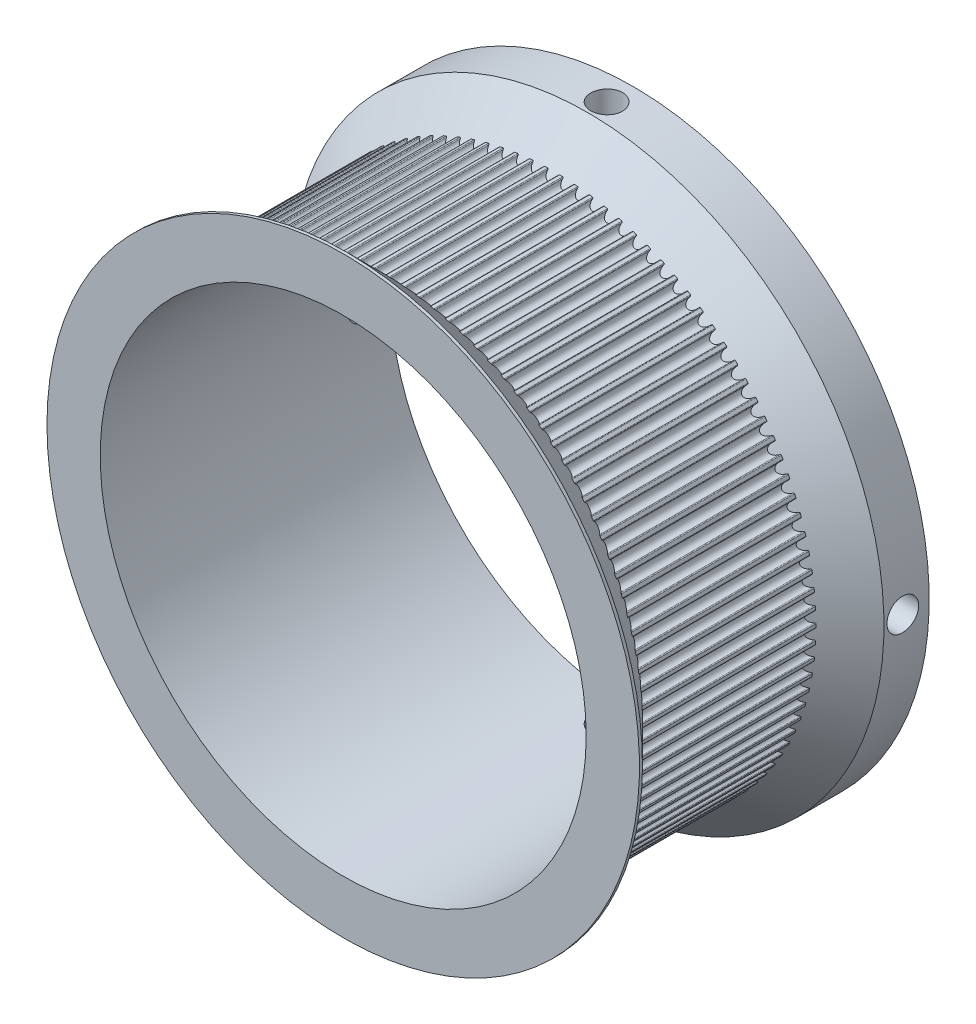
SolidWorks part; units mm, degrees
ref_plane "Front Plane" through (0, 0, 0) normal (0, 0, 1) x (1, 0, 0)
ref_plane "Top Plane" through (0, 0, 0) normal (0, 1, 0) x (1, 0, 0)
ref_plane "Right Plane" through (0, 0, 0) normal (1, 0, 0) x (0, 0, -1)
sketch "Sketch2" plane through (0, 0, 0) normal (0, 0, 1) x (1, 0, 0)
  circle A0 centre (0, 0) radius 35.0141 construction
  arc A1 (-2.7736, 34.6493) -> (-2.6556, 34.5527) centre (-2.7648, 34.5396) cw
  arc A2 (-2.6556, 34.5527) -> (-1.3004, 34.6302) centre (-1.9804, 34.6335) ccw
  arc A3 (-1.3004, 34.6302) -> (-1.1942, 34.7396) centre (-1.1904, 34.6296) cw
  arc A4 (-1.1942, 34.7396) -> (-0.791, 34.7511) centre (0, 0) cw
  circle A5 centre (0, 0) radius 34.7601 construction
  circle A6 centre (0, 0) radius 34.0101 construction
  arc A7 (0.791, 34.7511) -> (1.1942, 34.7396) centre (0, 0) cw
  arc A8 (0.6787, 34.6479) -> (0.791, 34.7511) centre (0.7885, 34.6411) cw
  arc A9 (-0.6787, 34.6479) -> (0.6787, 34.6479) centre (0, 34.6901) ccw
  arc A10 (-0.791, 34.7511) -> (-0.6787, 34.6479) centre (-0.7885, 34.6411) cw
  arc A11 (2.7736, 34.6493) -> (3.1755, 34.6147) centre (0, 0) cw
  arc A12 (2.6556, 34.5527) -> (2.7736, 34.6493) centre (2.7648, 34.5396) cw
  arc A13 (1.3004, 34.6302) -> (2.6556, 34.5527) centre (1.9804, 34.6335) ccw
  arc A14 (1.1942, 34.7396) -> (1.3004, 34.6302) centre (1.1904, 34.6296) cw
  arc A15 (4.7472, 34.4344) -> (5.1464, 34.377) centre (0, 0) cw
  arc A16 (4.6238, 34.3447) -> (4.7472, 34.4344) centre (4.7321, 34.3254) cw
  arc A17 (3.2753, 34.4995) -> (4.6238, 34.3447) centre (3.9544, 34.464) ccw
  arc A18 (3.1755, 34.6147) -> (3.2753, 34.4995) centre (3.1654, 34.5052) cw
  arc A19 (6.7052, 34.1072) -> (7.1006, 34.0271) centre (0, 0) cw
  arc A20 (6.577, 34.0247) -> (6.7052, 34.1072) centre (6.684, 33.9993) cw
  arc A21 (5.2395, 34.2562) -> (6.577, 34.0247) centre (5.9154, 34.182) ccw
  arc A22 (5.1464, 34.377) -> (5.2395, 34.2562) centre (5.1301, 34.2682) cw
  arc A23 (8.6414, 33.6688) -> (9.0316, 33.5663) centre (0, 0) cw
  arc A24 (8.5087, 33.5938) -> (8.6414, 33.6688) centre (8.6141, 33.5623) cw
  arc A25 (7.1866, 33.9012) -> (8.5087, 33.5938) centre (7.8572, 33.7886) ccw
  arc A26 (7.1006, 34.0271) -> (7.1866, 33.9012) centre (7.0781, 33.9194) cw
  arc A27 (10.5495, 33.1206) -> (10.9331, 32.9959) centre (0, 0) cw
  arc A28 (10.4127, 33.0532) -> (10.5495, 33.1206) centre (10.5161, 33.0158) cw
  arc A29 (9.1103, 33.4357) -> (10.4127, 33.0532) centre (9.7733, 33.2849) ccw
  arc A30 (9.0316, 33.5663) -> (9.1103, 33.4357) centre (9.003, 33.46) cw
  arc A31 (12.4231, 32.4643) -> (12.799, 32.318) centre (0, 0) cw
  arc A32 (12.2826, 32.4049) -> (12.4231, 32.4643) centre (12.3838, 32.3616) cw
  arc A33 (11.0042, 32.861) -> (12.2826, 32.4049) centre (11.6576, 32.6727) ccw
  arc A34 (10.9331, 32.9959) -> (11.0042, 32.861) centre (10.8985, 32.8915) cw
  arc A35 (14.2562, 31.7021) -> (14.6231, 31.5346) centre (0, 0) cw
  arc A36 (14.1126, 31.6508) -> (14.2562, 31.7021) centre (14.211, 31.6018) cw
  arc A37 (12.8622, 32.1792) -> (14.1126, 31.6508) centre (13.5038, 31.9539) ccw
  arc A38 (12.799, 32.318) -> (12.8622, 32.1792) centre (12.7585, 32.2157) cw
  arc A39 (16.0427, 30.8366) -> (16.3995, 30.6483) centre (0, 0) cw
  arc A40 (15.8965, 30.7935) -> (16.0427, 30.8366) centre (15.992, 30.739) cw
  arc A41 (14.6783, 31.3925) -> (15.8965, 30.7935) centre (15.306, 31.1308) ccw
  arc A42 (14.6231, 31.5346) -> (14.6783, 31.3925) centre (14.5768, 31.4348) cw
  arc A43 (17.777, 29.8704) -> (18.1224, 29.6621) centre (0, 0) cw
  arc A44 (17.6285, 29.8358) -> (17.777, 29.8704) centre (17.7207, 29.7759) cw
  arc A45 (16.4466, 30.5033) -> (17.6285, 29.8358) centre (17.0583, 30.2063) ccw
  arc A46 (16.3995, 30.6483) -> (16.4466, 30.5033) centre (16.3476, 30.5513) cw
  arc A47 (19.4533, 28.8068) -> (19.7863, 28.5791) centre (0, 0) cw
  arc A48 (19.303, 28.7808) -> (19.4533, 28.8068) centre (19.3917, 28.7157) cw
  arc A49 (18.1611, 29.5146) -> (19.303, 28.7808) centre (18.7549, 29.1832) ccw
  arc A50 (18.1224, 29.6621) -> (18.1611, 29.5146) centre (18.0651, 29.5682) cw
  arc A51 (21.0661, 27.6493) -> (21.3855, 27.403) centre (0, 0) cw
  arc A52 (20.9146, 27.6318) -> (21.0661, 27.6493) centre (20.9994, 27.5618) cw
  arc A53 (19.8165, 28.4297) -> (20.9146, 27.6318) centre (20.3903, 28.0649) ccw
  arc A54 (19.7863, 28.5791) -> (19.8165, 28.4297) centre (19.7236, 28.4887) cw
  arc A55 (22.6102, 26.4016) -> (22.9151, 26.1374) centre (0, 0) cw
  arc A56 (22.458, 26.3928) -> (22.6102, 26.4016) centre (22.5387, 26.318) cw
  arc A57 (21.4072, 27.252) -> (22.458, 26.3928) centre (21.9593, 26.855) ccw
  arc A58 (21.3855, 27.403) -> (21.4072, 27.252) centre (21.3179, 27.3162) cw
  arc A59 (24.0806, 25.0677) -> (24.3698, 24.7866) centre (0, 0) cw
  arc A60 (23.9281, 25.0676) -> (24.0806, 25.0677) centre (24.0044, 24.9884) cw
  arc A61 (22.928, 25.9855) -> (23.9281, 25.0676) centre (23.4566, 25.5576) ccw
  arc A62 (22.9151, 26.1374) -> (22.928, 25.9855) centre (22.8425, 26.0547) cw
  arc A63 (25.4724, 23.6521) -> (25.7451, 23.3549) centre (0, 0) cw
  arc A64 (25.3201, 23.6607) -> (25.4724, 23.6521) centre (25.3918, 23.5773) cw
  arc A65 (24.3741, 24.6342) -> (25.3201, 23.6607) centre (24.8774, 24.1768) ccw
  arc A66 (24.3698, 24.7866) -> (24.3741, 24.6342) centre (24.2927, 24.7081) cw
  arc A67 (26.7811, 22.1593) -> (27.0365, 21.8471) centre (0, 0) cw
  arc A68 (26.6296, 22.1767) -> (26.7811, 22.1593) centre (26.6964, 22.0892) cw
  arc A69 (25.7407, 23.2025) -> (26.6296, 22.1767) centre (26.217, 22.7172) ccw
  arc A70 (25.7451, 23.3549) -> (25.7407, 23.2025) centre (25.6637, 23.281) cw
  arc A71 (28.0025, 20.5943) -> (28.2396, 20.268) centre (0, 0) cw
  arc A72 (27.8522, 20.6202) -> (28.0025, 20.5943) centre (27.9139, 20.5291) cw
  arc A73 (27.0233, 21.6951) -> (27.8522, 20.6202) centre (27.4712, 21.1834) ccw
  arc A74 (27.0365, 21.8471) -> (27.0233, 21.6951) centre (26.9509, 21.7779) cw
  arc A75 (29.1325, 18.9621) -> (29.3506, 18.6227) centre (0, 0) cw
  arc A76 (28.984, 18.9966) -> (29.1325, 18.9621) centre (29.0403, 18.9021) cw
  arc A77 (28.2178, 20.117) -> (28.984, 18.9966) centre (28.6357, 19.5806) ccw
  arc A78 (28.2396, 20.268) -> (28.2178, 20.117) centre (28.1502, 20.2038) cw
  arc A79 (30.1675, 17.268) -> (30.3659, 16.9168) centre (0, 0) cw
  arc A80 (30.0212, 17.3109) -> (30.1675, 17.268) centre (30.0721, 17.2134) cw
  arc A81 (29.3202, 18.4733) -> (30.0212, 17.3109) centre (29.7068, 17.9139) ccw
  arc A82 (29.3506, 18.6227) -> (29.3202, 18.4733) centre (29.2577, 18.5638) cw
  arc A83 (31.1041, 15.5176) -> (31.2821, 15.1556) centre (0, 0) cw
  arc A84 (30.9605, 15.5688) -> (31.1041, 15.5176) centre (31.0057, 15.4685) cw
  arc A85 (30.3271, 16.7693) -> (30.9605, 15.5688) centre (30.6811, 16.1887) ccw
  arc A86 (30.3659, 16.9168) -> (30.3271, 16.7693) centre (30.2698, 16.8632) cw
  arc A87 (31.9393, 13.7166) -> (32.0963, 13.3451) centre (0, 0) cw
  arc A88 (31.7988, 13.7759) -> (31.9393, 13.7166) centre (31.8382, 13.6732) cw
  arc A89 (31.2349, 15.0106) -> (31.7988, 13.7759) centre (31.5552, 14.4108) ccw
  arc A90 (31.2821, 15.1556) -> (31.2349, 15.0106) centre (31.1831, 15.1077) cw
  arc A91 (32.6703, 11.8709) -> (32.8058, 11.4909) centre (0, 0) cw
  arc A92 (32.5334, 11.9381) -> (32.6703, 11.8709) centre (32.5669, 11.8333) cw
  arc A93 (32.0409, 13.203) -> (32.5334, 11.9381) centre (32.3264, 12.5858) ccw
  arc A94 (32.0963, 13.3451) -> (32.0409, 13.203) centre (31.9947, 13.3028) cw
  arc A95 (33.2947, 9.9864) -> (33.4083, 9.5994) centre (0, 0) cw
  arc A96 (33.1619, 10.0613) -> (33.2947, 9.9864) centre (33.1893, 9.9548) cw
  arc A97 (32.7424, 11.3523) -> (33.1619, 10.0613) centre (32.9922, 10.7198) ccw
  arc A98 (32.8058, 11.4909) -> (32.7424, 11.3523) centre (32.702, 11.4546) cw
  arc A99 (33.8105, 8.0694) -> (33.9019, 7.6765) centre (0, 0) cw
  arc A100 (33.6822, 8.1517) -> (33.8105, 8.0694) centre (33.7035, 8.0438) cw
  arc A101 (33.3371, 9.4645) -> (33.6822, 8.1517) centre (33.5504, 8.8189) ccw
  arc A102 (33.4083, 9.5994) -> (33.3371, 9.4645) centre (33.3026, 9.569) cw
  arc A103 (34.216, 6.126) -> (34.2848, 5.7285) centre (0, 0) cw
  arc A104 (34.0926, 6.2156) -> (34.216, 6.126) centre (34.1077, 6.1066) cw
  arc A105 (33.8231, 7.5459) -> (34.0926, 6.2156) centre (33.9991, 6.8891) ccw
  arc A106 (33.9019, 7.6765) -> (33.8231, 7.5459) centre (33.7946, 7.6522) cw
  arc A107 (34.5099, 4.1627) -> (34.5559, 3.7619) centre (0, 0) cw
  arc A108 (34.3919, 4.2591) -> (34.5099, 4.1627) centre (34.4007, 4.1495) cw
  arc A109 (34.1987, 5.6027) -> (34.3919, 4.2591) centre (34.337, 4.9369) ccw
  arc A110 (34.2848, 5.7285) -> (34.1987, 5.6027) centre (34.1763, 5.7104) cw
  arc A111 (34.6913, 2.1857) -> (34.7143, 1.783) centre (0, 0) cw
  arc A112 (34.5789, 2.2888) -> (34.6913, 2.1857) centre (34.5815, 2.1788) cw
  arc A113 (34.4628, 3.6412) -> (34.5789, 2.2888) centre (34.5628, 2.9686) ccw
  arc A114 (34.5559, 3.7619) -> (34.4628, 3.6412) centre (34.4466, 3.75) cw
  arc A115 (34.7595, 0.2017) -> (34.7595, -0.2017) centre (0, 0) cw
  arc A116 (34.6532, 0.311) -> (34.7595, 0.2017) centre (34.6495, 0.2011) cw
  arc A117 (34.6144, 1.6678) -> (34.6532, 0.311) centre (34.6759, 0.9906) ccw
  arc A118 (34.7143, 1.783) -> (34.6144, 1.6678) centre (34.6045, 1.7774) cw
  arc A119 (34.7143, -1.783) -> (34.6913, -2.1857) centre (0, 0) cw
  arc A120 (34.6144, -1.6678) -> (34.7143, -1.783) centre (34.6045, -1.7774) cw
  arc A121 (34.6532, -0.311) -> (34.6144, -1.6678) centre (34.6759, -0.9906) ccw
  arc A122 (34.7595, -0.2017) -> (34.6532, -0.311) centre (34.6495, -0.2011) cw
  arc A123 (34.5559, -3.7619) -> (34.5099, -4.1627) centre (0, 0) cw
  arc A124 (34.4628, -3.6412) -> (34.5559, -3.7619) centre (34.4466, -3.75) cw
  arc A125 (34.5789, -2.2888) -> (34.4628, -3.6412) centre (34.5628, -2.9686) ccw
  arc A126 (34.6913, -2.1857) -> (34.5789, -2.2888) centre (34.5815, -2.1788) cw
  arc A127 (34.2848, -5.7285) -> (34.216, -6.126) centre (0, 0) cw
  arc A128 (34.1987, -5.6027) -> (34.2848, -5.7285) centre (34.1763, -5.7104) cw
  arc A129 (34.3919, -4.2591) -> (34.1987, -5.6027) centre (34.337, -4.9369) ccw
  arc A130 (34.5099, -4.1627) -> (34.3919, -4.2591) centre (34.4007, -4.1495) cw
  arc A131 (33.9019, -7.6765) -> (33.8105, -8.0694) centre (0, 0) cw
  arc A132 (33.8231, -7.5459) -> (33.9019, -7.6765) centre (33.7946, -7.6522) cw
  arc A133 (34.0926, -6.2156) -> (33.8231, -7.5459) centre (33.9991, -6.8891) ccw
  arc A134 (34.216, -6.126) -> (34.0926, -6.2156) centre (34.1077, -6.1066) cw
  arc A135 (33.4083, -9.5994) -> (33.2947, -9.9864) centre (0, 0) cw
  arc A136 (33.3371, -9.4645) -> (33.4083, -9.5994) centre (33.3026, -9.569) cw
  arc A137 (33.6822, -8.1517) -> (33.3371, -9.4645) centre (33.5504, -8.8189) ccw
  arc A138 (33.8105, -8.0694) -> (33.6822, -8.1517) centre (33.7035, -8.0438) cw
  arc A139 (32.8058, -11.4909) -> (32.6703, -11.8709) centre (0, 0) cw
  arc A140 (32.7424, -11.3523) -> (32.8058, -11.4909) centre (32.702, -11.4546) cw
  arc A141 (33.1619, -10.0613) -> (32.7424, -11.3523) centre (32.9922, -10.7198) ccw
  arc A142 (33.2947, -9.9864) -> (33.1619, -10.0613) centre (33.1893, -9.9548) cw
  arc A143 (32.0963, -13.3451) -> (31.9393, -13.7166) centre (0, 0) cw
  arc A144 (32.0409, -13.203) -> (32.0963, -13.3451) centre (31.9947, -13.3028) cw
  arc A145 (32.5334, -11.9381) -> (32.0409, -13.203) centre (32.3264, -12.5858) ccw
  arc A146 (32.6703, -11.8709) -> (32.5334, -11.9381) centre (32.5669, -11.8333) cw
  arc A147 (31.2821, -15.1556) -> (31.1041, -15.5176) centre (0, 0) cw
  arc A148 (31.2349, -15.0106) -> (31.2821, -15.1556) centre (31.1831, -15.1077) cw
  arc A149 (31.7988, -13.7759) -> (31.2349, -15.0106) centre (31.5552, -14.4108) ccw
  arc A150 (31.9393, -13.7166) -> (31.7988, -13.7759) centre (31.8382, -13.6732) cw
  arc A151 (30.3659, -16.9168) -> (30.1675, -17.268) centre (0, 0) cw
  arc A152 (30.3271, -16.7693) -> (30.3659, -16.9168) centre (30.2698, -16.8632) cw
  arc A153 (30.9605, -15.5688) -> (30.3271, -16.7693) centre (30.6811, -16.1887) ccw
  arc A154 (31.1041, -15.5176) -> (30.9605, -15.5688) centre (31.0057, -15.4685) cw
  arc A155 (29.3506, -18.6227) -> (29.1325, -18.9621) centre (0, 0) cw
  arc A156 (29.3202, -18.4733) -> (29.3506, -18.6227) centre (29.2577, -18.5638) cw
  arc A157 (30.0212, -17.3109) -> (29.3202, -18.4733) centre (29.7068, -17.9139) ccw
  arc A158 (30.1675, -17.268) -> (30.0212, -17.3109) centre (30.0721, -17.2134) cw
  arc A159 (28.2396, -20.268) -> (28.0025, -20.5943) centre (0, 0) cw
  arc A160 (28.2178, -20.117) -> (28.2396, -20.268) centre (28.1502, -20.2038) cw
  arc A161 (28.984, -18.9966) -> (28.2178, -20.117) centre (28.6357, -19.5806) ccw
  arc A162 (29.1325, -18.9621) -> (28.984, -18.9966) centre (29.0403, -18.9021) cw
  arc A163 (27.0365, -21.8471) -> (26.7811, -22.1593) centre (0, 0) cw
  arc A164 (27.0233, -21.6951) -> (27.0365, -21.8471) centre (26.9509, -21.7779) cw
  arc A165 (27.8522, -20.6202) -> (27.0233, -21.6951) centre (27.4712, -21.1834) ccw
  arc A166 (28.0025, -20.5943) -> (27.8522, -20.6202) centre (27.9139, -20.5291) cw
  arc A167 (25.7451, -23.3549) -> (25.4724, -23.6521) centre (0, 0) cw
  arc A168 (25.7407, -23.2025) -> (25.7451, -23.3549) centre (25.6637, -23.281) cw
  arc A169 (26.6296, -22.1767) -> (25.7407, -23.2025) centre (26.217, -22.7172) ccw
  arc A170 (26.7811, -22.1593) -> (26.6296, -22.1767) centre (26.6964, -22.0892) cw
  arc A171 (24.3698, -24.7866) -> (24.0806, -25.0677) centre (0, 0) cw
  arc A172 (24.3741, -24.6342) -> (24.3698, -24.7866) centre (24.2927, -24.7081) cw
  arc A173 (25.3201, -23.6607) -> (24.3741, -24.6342) centre (24.8774, -24.1768) ccw
  arc A174 (25.4724, -23.6521) -> (25.3201, -23.6607) centre (25.3918, -23.5773) cw
  arc A175 (22.9151, -26.1374) -> (22.6102, -26.4016) centre (0, 0) cw
  arc A176 (22.928, -25.9855) -> (22.9151, -26.1374) centre (22.8425, -26.0547) cw
  arc A177 (23.9281, -25.0676) -> (22.928, -25.9855) centre (23.4566, -25.5576) ccw
  arc A178 (24.0806, -25.0677) -> (23.9281, -25.0676) centre (24.0044, -24.9884) cw
  arc A179 (21.3855, -27.403) -> (21.0661, -27.6493) centre (0, 0) cw
  arc A180 (21.4072, -27.252) -> (21.3855, -27.403) centre (21.3179, -27.3162) cw
  arc A181 (22.458, -26.3928) -> (21.4072, -27.252) centre (21.9593, -26.855) ccw
  arc A182 (22.6102, -26.4016) -> (22.458, -26.3928) centre (22.5387, -26.318) cw
  arc A183 (19.7863, -28.5791) -> (19.4533, -28.8068) centre (0, 0) cw
  arc A184 (19.8165, -28.4297) -> (19.7863, -28.5791) centre (19.7236, -28.4887) cw
  arc A185 (20.9146, -27.6318) -> (19.8165, -28.4297) centre (20.3903, -28.0649) ccw
  arc A186 (21.0661, -27.6493) -> (20.9146, -27.6318) centre (20.9994, -27.5618) cw
  arc A187 (18.1224, -29.6621) -> (17.777, -29.8704) centre (0, 0) cw
  arc A188 (18.1611, -29.5146) -> (18.1224, -29.6621) centre (18.0651, -29.5682) cw
  arc A189 (19.303, -28.7808) -> (18.1611, -29.5146) centre (18.7549, -29.1832) ccw
  arc A190 (19.4533, -28.8068) -> (19.303, -28.7808) centre (19.3917, -28.7157) cw
  arc A191 (16.3995, -30.6483) -> (16.0427, -30.8366) centre (0, 0) cw
  arc A192 (16.4466, -30.5033) -> (16.3995, -30.6483) centre (16.3476, -30.5513) cw
  arc A193 (17.6285, -29.8358) -> (16.4466, -30.5033) centre (17.0583, -30.2063) ccw
  arc A194 (17.777, -29.8704) -> (17.6285, -29.8358) centre (17.7207, -29.7759) cw
  arc A195 (14.6231, -31.5346) -> (14.2562, -31.7021) centre (0, 0) cw
  arc A196 (14.6783, -31.3925) -> (14.6231, -31.5346) centre (14.5768, -31.4348) cw
  arc A197 (15.8965, -30.7935) -> (14.6783, -31.3925) centre (15.306, -31.1308) ccw
  arc A198 (16.0427, -30.8366) -> (15.8965, -30.7935) centre (15.992, -30.739) cw
  arc A199 (12.799, -32.318) -> (12.4231, -32.4643) centre (0, 0) cw
  arc A200 (12.8622, -32.1792) -> (12.799, -32.318) centre (12.7585, -32.2157) cw
  arc A201 (14.1126, -31.6508) -> (12.8622, -32.1792) centre (13.5038, -31.9539) ccw
  arc A202 (14.2562, -31.7021) -> (14.1126, -31.6508) centre (14.211, -31.6018) cw
  arc A203 (10.9331, -32.9959) -> (10.5495, -33.1206) centre (0, 0) cw
  arc A204 (11.0042, -32.861) -> (10.9331, -32.9959) centre (10.8985, -32.8915) cw
  arc A205 (12.2826, -32.4049) -> (11.0042, -32.861) centre (11.6576, -32.6727) ccw
  arc A206 (12.4231, -32.4643) -> (12.2826, -32.4049) centre (12.3838, -32.3616) cw
  arc A207 (9.0316, -33.5663) -> (8.6414, -33.6688) centre (0, 0) cw
  arc A208 (9.1103, -33.4357) -> (9.0316, -33.5663) centre (9.003, -33.46) cw
  arc A209 (10.4127, -33.0532) -> (9.1103, -33.4357) centre (9.7733, -33.2849) ccw
  arc A210 (10.5495, -33.1206) -> (10.4127, -33.0532) centre (10.5161, -33.0158) cw
  arc A211 (7.1006, -34.0271) -> (6.7052, -34.1072) centre (0, 0) cw
  arc A212 (7.1866, -33.9012) -> (7.1006, -34.0271) centre (7.0781, -33.9194) cw
  arc A213 (8.5087, -33.5938) -> (7.1866, -33.9012) centre (7.8572, -33.7886) ccw
  arc A214 (8.6414, -33.6688) -> (8.5087, -33.5938) centre (8.6141, -33.5623) cw
  arc A215 (5.1464, -34.377) -> (4.7472, -34.4344) centre (0, 0) cw
  arc A216 (5.2395, -34.2562) -> (5.1464, -34.377) centre (5.1301, -34.2682) cw
  arc A217 (6.577, -34.0247) -> (5.2395, -34.2562) centre (5.9154, -34.182) ccw
  arc A218 (6.7052, -34.1072) -> (6.577, -34.0247) centre (6.684, -33.9993) cw
  arc A219 (3.1755, -34.6147) -> (2.7736, -34.6493) centre (0, 0) cw
  arc A220 (3.2753, -34.4995) -> (3.1755, -34.6147) centre (3.1654, -34.5052) cw
  arc A221 (4.6238, -34.3447) -> (3.2753, -34.4995) centre (3.9544, -34.464) ccw
  arc A222 (4.7472, -34.4344) -> (4.6238, -34.3447) centre (4.7321, -34.3254) cw
  arc A223 (1.1942, -34.7396) -> (0.791, -34.7511) centre (0, 0) cw
  arc A224 (1.3004, -34.6302) -> (1.1942, -34.7396) centre (1.1904, -34.6296) cw
  arc A225 (2.6556, -34.5527) -> (1.3004, -34.6302) centre (1.9804, -34.6335) ccw
  arc A226 (2.7736, -34.6493) -> (2.6556, -34.5527) centre (2.7648, -34.5396) cw
  arc A227 (-0.791, -34.7511) -> (-1.1942, -34.7396) centre (0, 0) cw
  arc A228 (-0.6787, -34.6479) -> (-0.791, -34.7511) centre (-0.7885, -34.6411) cw
  arc A229 (0.6787, -34.6479) -> (-0.6787, -34.6479) centre (0, -34.6901) ccw
  arc A230 (0.791, -34.7511) -> (0.6787, -34.6479) centre (0.7885, -34.6411) cw
  arc A231 (-2.7736, -34.6493) -> (-3.1755, -34.6147) centre (0, 0) cw
  arc A232 (-2.6556, -34.5527) -> (-2.7736, -34.6493) centre (-2.7648, -34.5396) cw
  arc A233 (-1.3004, -34.6302) -> (-2.6556, -34.5527) centre (-1.9804, -34.6335) ccw
  arc A234 (-1.1942, -34.7396) -> (-1.3004, -34.6302) centre (-1.1904, -34.6296) cw
  arc A235 (-4.7472, -34.4344) -> (-5.1464, -34.377) centre (0, 0) cw
  arc A236 (-4.6238, -34.3447) -> (-4.7472, -34.4344) centre (-4.7321, -34.3254) cw
  arc A237 (-3.2753, -34.4995) -> (-4.6238, -34.3447) centre (-3.9544, -34.464) ccw
  arc A238 (-3.1755, -34.6147) -> (-3.2753, -34.4995) centre (-3.1654, -34.5052) cw
  arc A239 (-6.7052, -34.1072) -> (-7.1006, -34.0271) centre (0, 0) cw
  arc A240 (-6.577, -34.0247) -> (-6.7052, -34.1072) centre (-6.684, -33.9993) cw
  arc A241 (-5.2395, -34.2562) -> (-6.577, -34.0247) centre (-5.9154, -34.182) ccw
  arc A242 (-5.1464, -34.377) -> (-5.2395, -34.2562) centre (-5.1301, -34.2682) cw
  arc A243 (-8.6414, -33.6688) -> (-9.0316, -33.5663) centre (0, 0) cw
  arc A244 (-8.5087, -33.5938) -> (-8.6414, -33.6688) centre (-8.6141, -33.5623) cw
  arc A245 (-7.1866, -33.9012) -> (-8.5087, -33.5938) centre (-7.8572, -33.7886) ccw
  arc A246 (-7.1006, -34.0271) -> (-7.1866, -33.9012) centre (-7.0781, -33.9194) cw
  arc A247 (-10.5495, -33.1206) -> (-10.9331, -32.9959) centre (0, 0) cw
  arc A248 (-10.4127, -33.0532) -> (-10.5495, -33.1206) centre (-10.5161, -33.0158) cw
  arc A249 (-9.1103, -33.4357) -> (-10.4127, -33.0532) centre (-9.7733, -33.2849) ccw
  arc A250 (-9.0316, -33.5663) -> (-9.1103, -33.4357) centre (-9.003, -33.46) cw
  arc A251 (-12.4231, -32.4643) -> (-12.799, -32.318) centre (0, 0) cw
  arc A252 (-12.2826, -32.4049) -> (-12.4231, -32.4643) centre (-12.3838, -32.3616) cw
  arc A253 (-11.0042, -32.861) -> (-12.2826, -32.4049) centre (-11.6576, -32.6727) ccw
  arc A254 (-10.9331, -32.9959) -> (-11.0042, -32.861) centre (-10.8985, -32.8915) cw
  arc A255 (-14.2562, -31.7021) -> (-14.6231, -31.5346) centre (0, 0) cw
  arc A256 (-14.1126, -31.6508) -> (-14.2562, -31.7021) centre (-14.211, -31.6018) cw
  arc A257 (-12.8622, -32.1792) -> (-14.1126, -31.6508) centre (-13.5038, -31.9539) ccw
  arc A258 (-12.799, -32.318) -> (-12.8622, -32.1792) centre (-12.7585, -32.2157) cw
  arc A259 (-16.0427, -30.8366) -> (-16.3995, -30.6483) centre (0, 0) cw
  arc A260 (-15.8965, -30.7935) -> (-16.0427, -30.8366) centre (-15.992, -30.739) cw
  arc A261 (-14.6783, -31.3925) -> (-15.8965, -30.7935) centre (-15.306, -31.1308) ccw
  arc A262 (-14.6231, -31.5346) -> (-14.6783, -31.3925) centre (-14.5768, -31.4348) cw
  arc A263 (-17.777, -29.8704) -> (-18.1224, -29.6621) centre (0, 0) cw
  arc A264 (-17.6285, -29.8358) -> (-17.777, -29.8704) centre (-17.7207, -29.7759) cw
  arc A265 (-16.4466, -30.5033) -> (-17.6285, -29.8358) centre (-17.0583, -30.2063) ccw
  arc A266 (-16.3995, -30.6483) -> (-16.4466, -30.5033) centre (-16.3476, -30.5513) cw
  arc A267 (-19.4533, -28.8068) -> (-19.7863, -28.5791) centre (0, 0) cw
  arc A268 (-19.303, -28.7808) -> (-19.4533, -28.8068) centre (-19.3917, -28.7157) cw
  arc A269 (-18.1611, -29.5146) -> (-19.303, -28.7808) centre (-18.7549, -29.1832) ccw
  arc A270 (-18.1224, -29.6621) -> (-18.1611, -29.5146) centre (-18.0651, -29.5682) cw
  arc A271 (-21.0661, -27.6493) -> (-21.3855, -27.403) centre (0, 0) cw
  arc A272 (-20.9146, -27.6318) -> (-21.0661, -27.6493) centre (-20.9994, -27.5618) cw
  arc A273 (-19.8165, -28.4297) -> (-20.9146, -27.6318) centre (-20.3903, -28.0649) ccw
  arc A274 (-19.7863, -28.5791) -> (-19.8165, -28.4297) centre (-19.7236, -28.4887) cw
  arc A275 (-22.6102, -26.4016) -> (-22.9151, -26.1374) centre (0, 0) cw
  arc A276 (-22.458, -26.3928) -> (-22.6102, -26.4016) centre (-22.5387, -26.318) cw
  arc A277 (-21.4072, -27.252) -> (-22.458, -26.3928) centre (-21.9593, -26.855) ccw
  arc A278 (-21.3855, -27.403) -> (-21.4072, -27.252) centre (-21.3179, -27.3162) cw
  arc A279 (-24.0806, -25.0677) -> (-24.3698, -24.7866) centre (0, 0) cw
  arc A280 (-23.9281, -25.0676) -> (-24.0806, -25.0677) centre (-24.0044, -24.9884) cw
  arc A281 (-22.928, -25.9855) -> (-23.9281, -25.0676) centre (-23.4566, -25.5576) ccw
  arc A282 (-22.9151, -26.1374) -> (-22.928, -25.9855) centre (-22.8425, -26.0547) cw
  arc A283 (-25.4724, -23.6521) -> (-25.7451, -23.3549) centre (0, 0) cw
  arc A284 (-25.3201, -23.6607) -> (-25.4724, -23.6521) centre (-25.3918, -23.5773) cw
  arc A285 (-24.3741, -24.6342) -> (-25.3201, -23.6607) centre (-24.8774, -24.1768) ccw
  arc A286 (-24.3698, -24.7866) -> (-24.3741, -24.6342) centre (-24.2927, -24.7081) cw
  arc A287 (-26.7811, -22.1593) -> (-27.0365, -21.8471) centre (0, 0) cw
  arc A288 (-26.6296, -22.1767) -> (-26.7811, -22.1593) centre (-26.6964, -22.0892) cw
  arc A289 (-25.7407, -23.2025) -> (-26.6296, -22.1767) centre (-26.217, -22.7172) ccw
  arc A290 (-25.7451, -23.3549) -> (-25.7407, -23.2025) centre (-25.6637, -23.281) cw
  arc A291 (-28.0025, -20.5943) -> (-28.2396, -20.268) centre (0, 0) cw
  arc A292 (-27.8522, -20.6202) -> (-28.0025, -20.5943) centre (-27.9139, -20.5291) cw
  arc A293 (-27.0233, -21.6951) -> (-27.8522, -20.6202) centre (-27.4712, -21.1834) ccw
  arc A294 (-27.0365, -21.8471) -> (-27.0233, -21.6951) centre (-26.9509, -21.7779) cw
  arc A295 (-29.1325, -18.9621) -> (-29.3506, -18.6227) centre (0, 0) cw
  arc A296 (-28.984, -18.9966) -> (-29.1325, -18.9621) centre (-29.0403, -18.9021) cw
  arc A297 (-28.2178, -20.117) -> (-28.984, -18.9966) centre (-28.6357, -19.5806) ccw
  arc A298 (-28.2396, -20.268) -> (-28.2178, -20.117) centre (-28.1502, -20.2038) cw
  arc A299 (-30.1675, -17.268) -> (-30.3659, -16.9168) centre (0, 0) cw
  arc A300 (-30.0212, -17.3109) -> (-30.1675, -17.268) centre (-30.0721, -17.2134) cw
  arc A301 (-29.3202, -18.4733) -> (-30.0212, -17.3109) centre (-29.7068, -17.9139) ccw
  arc A302 (-29.3506, -18.6227) -> (-29.3202, -18.4733) centre (-29.2577, -18.5638) cw
  arc A303 (-31.1041, -15.5176) -> (-31.2821, -15.1556) centre (0, 0) cw
  arc A304 (-30.9605, -15.5688) -> (-31.1041, -15.5176) centre (-31.0057, -15.4685) cw
  arc A305 (-30.3271, -16.7693) -> (-30.9605, -15.5688) centre (-30.6811, -16.1887) ccw
  arc A306 (-30.3659, -16.9168) -> (-30.3271, -16.7693) centre (-30.2698, -16.8632) cw
  arc A307 (-31.9393, -13.7166) -> (-32.0963, -13.3451) centre (0, 0) cw
  arc A308 (-31.7988, -13.7759) -> (-31.9393, -13.7166) centre (-31.8382, -13.6732) cw
  arc A309 (-31.2349, -15.0106) -> (-31.7988, -13.7759) centre (-31.5552, -14.4108) ccw
  arc A310 (-31.2821, -15.1556) -> (-31.2349, -15.0106) centre (-31.1831, -15.1077) cw
  arc A311 (-32.6703, -11.8709) -> (-32.8058, -11.4909) centre (0, 0) cw
  arc A312 (-32.5334, -11.9381) -> (-32.6703, -11.8709) centre (-32.5669, -11.8333) cw
  arc A313 (-32.0409, -13.203) -> (-32.5334, -11.9381) centre (-32.3264, -12.5858) ccw
  arc A314 (-32.0963, -13.3451) -> (-32.0409, -13.203) centre (-31.9947, -13.3028) cw
  arc A315 (-33.2947, -9.9864) -> (-33.4083, -9.5994) centre (0, 0) cw
  arc A316 (-33.1619, -10.0613) -> (-33.2947, -9.9864) centre (-33.1893, -9.9548) cw
  arc A317 (-32.7424, -11.3523) -> (-33.1619, -10.0613) centre (-32.9922, -10.7198) ccw
  arc A318 (-32.8058, -11.4909) -> (-32.7424, -11.3523) centre (-32.702, -11.4546) cw
  arc A319 (-33.8105, -8.0694) -> (-33.9019, -7.6765) centre (0, 0) cw
  arc A320 (-33.6822, -8.1517) -> (-33.8105, -8.0694) centre (-33.7035, -8.0438) cw
  arc A321 (-33.3371, -9.4645) -> (-33.6822, -8.1517) centre (-33.5504, -8.8189) ccw
  arc A322 (-33.4083, -9.5994) -> (-33.3371, -9.4645) centre (-33.3026, -9.569) cw
  arc A323 (-34.216, -6.126) -> (-34.2848, -5.7285) centre (0, 0) cw
  arc A324 (-34.0926, -6.2156) -> (-34.216, -6.126) centre (-34.1077, -6.1066) cw
  arc A325 (-33.8231, -7.5459) -> (-34.0926, -6.2156) centre (-33.9991, -6.8891) ccw
  arc A326 (-33.9019, -7.6765) -> (-33.8231, -7.5459) centre (-33.7946, -7.6522) cw
  arc A327 (-34.5099, -4.1627) -> (-34.5559, -3.7619) centre (0, 0) cw
  arc A328 (-34.3919, -4.2591) -> (-34.5099, -4.1627) centre (-34.4007, -4.1495) cw
  arc A329 (-34.1987, -5.6027) -> (-34.3919, -4.2591) centre (-34.337, -4.9369) ccw
  arc A330 (-34.2848, -5.7285) -> (-34.1987, -5.6027) centre (-34.1763, -5.7104) cw
  arc A331 (-34.6913, -2.1857) -> (-34.7143, -1.783) centre (0, 0) cw
  arc A332 (-34.5789, -2.2888) -> (-34.6913, -2.1857) centre (-34.5815, -2.1788) cw
  arc A333 (-34.4628, -3.6412) -> (-34.5789, -2.2888) centre (-34.5628, -2.9686) ccw
  arc A334 (-34.5559, -3.7619) -> (-34.4628, -3.6412) centre (-34.4466, -3.75) cw
  arc A335 (-34.7595, -0.2017) -> (-34.7595, 0.2017) centre (0, 0) cw
  arc A336 (-34.6532, -0.311) -> (-34.7595, -0.2017) centre (-34.6495, -0.2011) cw
  arc A337 (-34.6144, -1.6678) -> (-34.6532, -0.311) centre (-34.6759, -0.9906) ccw
  arc A338 (-34.7143, -1.783) -> (-34.6144, -1.6678) centre (-34.6045, -1.7774) cw
  arc A339 (-34.7143, 1.783) -> (-34.6913, 2.1857) centre (0, 0) cw
  arc A340 (-34.6144, 1.6678) -> (-34.7143, 1.783) centre (-34.6045, 1.7774) cw
  arc A341 (-34.6532, 0.311) -> (-34.6144, 1.6678) centre (-34.6759, 0.9906) ccw
  arc A342 (-34.7595, 0.2017) -> (-34.6532, 0.311) centre (-34.6495, 0.2011) cw
  arc A343 (-34.5559, 3.7619) -> (-34.5099, 4.1627) centre (0, 0) cw
  arc A344 (-34.4628, 3.6412) -> (-34.5559, 3.7619) centre (-34.4466, 3.75) cw
  arc A345 (-34.5789, 2.2888) -> (-34.4628, 3.6412) centre (-34.5628, 2.9686) ccw
  arc A346 (-34.6913, 2.1857) -> (-34.5789, 2.2888) centre (-34.5815, 2.1788) cw
  arc A347 (-34.2848, 5.7285) -> (-34.216, 6.126) centre (0, 0) cw
  arc A348 (-34.1987, 5.6027) -> (-34.2848, 5.7285) centre (-34.1763, 5.7104) cw
  arc A349 (-34.3919, 4.2591) -> (-34.1987, 5.6027) centre (-34.337, 4.9369) ccw
  arc A350 (-34.5099, 4.1627) -> (-34.3919, 4.2591) centre (-34.4007, 4.1495) cw
  arc A351 (-33.9019, 7.6765) -> (-33.8105, 8.0694) centre (0, 0) cw
  arc A352 (-33.8231, 7.5459) -> (-33.9019, 7.6765) centre (-33.7946, 7.6522) cw
  arc A353 (-34.0926, 6.2156) -> (-33.8231, 7.5459) centre (-33.9991, 6.8891) ccw
  arc A354 (-34.216, 6.126) -> (-34.0926, 6.2156) centre (-34.1077, 6.1066) cw
  arc A355 (-33.4083, 9.5994) -> (-33.2947, 9.9864) centre (0, 0) cw
  arc A356 (-33.3371, 9.4645) -> (-33.4083, 9.5994) centre (-33.3026, 9.569) cw
  arc A357 (-33.6822, 8.1517) -> (-33.3371, 9.4645) centre (-33.5504, 8.8189) ccw
  arc A358 (-33.8105, 8.0694) -> (-33.6822, 8.1517) centre (-33.7035, 8.0438) cw
  arc A359 (-32.8058, 11.4909) -> (-32.6703, 11.8709) centre (0, 0) cw
  arc A360 (-32.7424, 11.3523) -> (-32.8058, 11.4909) centre (-32.702, 11.4546) cw
  arc A361 (-33.1619, 10.0613) -> (-32.7424, 11.3523) centre (-32.9922, 10.7198) ccw
  arc A362 (-33.2947, 9.9864) -> (-33.1619, 10.0613) centre (-33.1893, 9.9548) cw
  arc A363 (-32.0963, 13.3451) -> (-31.9393, 13.7166) centre (0, 0) cw
  arc A364 (-32.0409, 13.203) -> (-32.0963, 13.3451) centre (-31.9947, 13.3028) cw
  arc A365 (-32.5334, 11.9381) -> (-32.0409, 13.203) centre (-32.3264, 12.5858) ccw
  arc A366 (-32.6703, 11.8709) -> (-32.5334, 11.9381) centre (-32.5669, 11.8333) cw
  arc A367 (-31.2821, 15.1556) -> (-31.1041, 15.5176) centre (0, 0) cw
  arc A368 (-31.2349, 15.0106) -> (-31.2821, 15.1556) centre (-31.1831, 15.1077) cw
  arc A369 (-31.7988, 13.7759) -> (-31.2349, 15.0106) centre (-31.5552, 14.4108) ccw
  arc A370 (-31.9393, 13.7166) -> (-31.7988, 13.7759) centre (-31.8382, 13.6732) cw
  arc A371 (-30.3659, 16.9168) -> (-30.1675, 17.268) centre (0, 0) cw
  arc A372 (-30.3271, 16.7693) -> (-30.3659, 16.9168) centre (-30.2698, 16.8632) cw
  arc A373 (-30.9605, 15.5688) -> (-30.3271, 16.7693) centre (-30.6811, 16.1887) ccw
  arc A374 (-31.1041, 15.5176) -> (-30.9605, 15.5688) centre (-31.0057, 15.4685) cw
  arc A375 (-29.3506, 18.6227) -> (-29.1325, 18.9621) centre (0, 0) cw
  arc A376 (-29.3202, 18.4733) -> (-29.3506, 18.6227) centre (-29.2577, 18.5638) cw
  arc A377 (-30.0212, 17.3109) -> (-29.3202, 18.4733) centre (-29.7068, 17.9139) ccw
  arc A378 (-30.1675, 17.268) -> (-30.0212, 17.3109) centre (-30.0721, 17.2134) cw
  arc A379 (-28.2396, 20.268) -> (-28.0025, 20.5943) centre (0, 0) cw
  arc A380 (-28.2178, 20.117) -> (-28.2396, 20.268) centre (-28.1502, 20.2038) cw
  arc A381 (-28.984, 18.9966) -> (-28.2178, 20.117) centre (-28.6357, 19.5806) ccw
  arc A382 (-29.1325, 18.9621) -> (-28.984, 18.9966) centre (-29.0403, 18.9021) cw
  arc A383 (-27.0365, 21.8471) -> (-26.7811, 22.1593) centre (0, 0) cw
  arc A384 (-27.0233, 21.6951) -> (-27.0365, 21.8471) centre (-26.9509, 21.7779) cw
  arc A385 (-27.8522, 20.6202) -> (-27.0233, 21.6951) centre (-27.4712, 21.1834) ccw
  arc A386 (-28.0025, 20.5943) -> (-27.8522, 20.6202) centre (-27.9139, 20.5291) cw
  arc A387 (-25.7451, 23.3549) -> (-25.4724, 23.6521) centre (0, 0) cw
  arc A388 (-25.7407, 23.2025) -> (-25.7451, 23.3549) centre (-25.6637, 23.281) cw
  arc A389 (-26.6296, 22.1767) -> (-25.7407, 23.2025) centre (-26.217, 22.7172) ccw
  arc A390 (-26.7811, 22.1593) -> (-26.6296, 22.1767) centre (-26.6964, 22.0892) cw
  arc A391 (-24.3698, 24.7866) -> (-24.0806, 25.0677) centre (0, 0) cw
  arc A392 (-24.3741, 24.6342) -> (-24.3698, 24.7866) centre (-24.2927, 24.7081) cw
  arc A393 (-25.3201, 23.6607) -> (-24.3741, 24.6342) centre (-24.8774, 24.1768) ccw
  arc A394 (-25.4724, 23.6521) -> (-25.3201, 23.6607) centre (-25.3918, 23.5773) cw
  arc A395 (-22.9151, 26.1374) -> (-22.6102, 26.4016) centre (0, 0) cw
  arc A396 (-22.928, 25.9855) -> (-22.9151, 26.1374) centre (-22.8425, 26.0547) cw
  arc A397 (-23.9281, 25.0676) -> (-22.928, 25.9855) centre (-23.4566, 25.5576) ccw
  arc A398 (-24.0806, 25.0677) -> (-23.9281, 25.0676) centre (-24.0044, 24.9884) cw
  arc A399 (-21.3855, 27.403) -> (-21.0661, 27.6493) centre (0, 0) cw
  arc A400 (-21.4072, 27.252) -> (-21.3855, 27.403) centre (-21.3179, 27.3162) cw
  arc A401 (-22.458, 26.3928) -> (-21.4072, 27.252) centre (-21.9593, 26.855) ccw
  arc A402 (-22.6102, 26.4016) -> (-22.458, 26.3928) centre (-22.5387, 26.318) cw
  arc A403 (-19.7863, 28.5791) -> (-19.4533, 28.8068) centre (0, 0) cw
  arc A404 (-19.8165, 28.4297) -> (-19.7863, 28.5791) centre (-19.7236, 28.4887) cw
  arc A405 (-20.9146, 27.6318) -> (-19.8165, 28.4297) centre (-20.3903, 28.0649) ccw
  arc A406 (-21.0661, 27.6493) -> (-20.9146, 27.6318) centre (-20.9994, 27.5618) cw
  arc A407 (-18.1224, 29.6621) -> (-17.777, 29.8704) centre (0, 0) cw
  arc A408 (-18.1611, 29.5146) -> (-18.1224, 29.6621) centre (-18.0651, 29.5682) cw
  arc A409 (-19.303, 28.7808) -> (-18.1611, 29.5146) centre (-18.7549, 29.1832) ccw
  arc A410 (-19.4533, 28.8068) -> (-19.303, 28.7808) centre (-19.3917, 28.7157) cw
  arc A411 (-16.3995, 30.6483) -> (-16.0427, 30.8366) centre (0, 0) cw
  arc A412 (-16.4466, 30.5033) -> (-16.3995, 30.6483) centre (-16.3476, 30.5513) cw
  arc A413 (-17.6285, 29.8358) -> (-16.4466, 30.5033) centre (-17.0583, 30.2063) ccw
  arc A414 (-17.777, 29.8704) -> (-17.6285, 29.8358) centre (-17.7207, 29.7759) cw
  arc A415 (-14.6231, 31.5346) -> (-14.2562, 31.7021) centre (0, 0) cw
  arc A416 (-14.6783, 31.3925) -> (-14.6231, 31.5346) centre (-14.5768, 31.4348) cw
  arc A417 (-15.8965, 30.7935) -> (-14.6783, 31.3925) centre (-15.306, 31.1308) ccw
  arc A418 (-16.0427, 30.8366) -> (-15.8965, 30.7935) centre (-15.992, 30.739) cw
  arc A419 (-12.799, 32.318) -> (-12.4231, 32.4643) centre (0, 0) cw
  arc A420 (-12.8622, 32.1792) -> (-12.799, 32.318) centre (-12.7585, 32.2157) cw
  arc A421 (-14.1126, 31.6508) -> (-12.8622, 32.1792) centre (-13.5038, 31.9539) ccw
  arc A422 (-14.2562, 31.7021) -> (-14.1126, 31.6508) centre (-14.211, 31.6018) cw
  arc A423 (-10.9331, 32.9959) -> (-10.5495, 33.1206) centre (0, 0) cw
  arc A424 (-11.0042, 32.861) -> (-10.9331, 32.9959) centre (-10.8985, 32.8915) cw
  arc A425 (-12.2826, 32.4049) -> (-11.0042, 32.861) centre (-11.6576, 32.6727) ccw
  arc A426 (-12.4231, 32.4643) -> (-12.2826, 32.4049) centre (-12.3838, 32.3616) cw
  arc A427 (-9.0316, 33.5663) -> (-8.6414, 33.6688) centre (0, 0) cw
  arc A428 (-9.1103, 33.4357) -> (-9.0316, 33.5663) centre (-9.003, 33.46) cw
  arc A429 (-10.4127, 33.0532) -> (-9.1103, 33.4357) centre (-9.7733, 33.2849) ccw
  arc A430 (-10.5495, 33.1206) -> (-10.4127, 33.0532) centre (-10.5161, 33.0158) cw
  arc A431 (-7.1006, 34.0271) -> (-6.7052, 34.1072) centre (0, 0) cw
  arc A432 (-7.1866, 33.9012) -> (-7.1006, 34.0271) centre (-7.0781, 33.9194) cw
  arc A433 (-8.5087, 33.5938) -> (-7.1866, 33.9012) centre (-7.8572, 33.7886) ccw
  arc A434 (-8.6414, 33.6688) -> (-8.5087, 33.5938) centre (-8.6141, 33.5623) cw
  arc A435 (-5.1464, 34.377) -> (-4.7472, 34.4344) centre (0, 0) cw
  arc A436 (-5.2395, 34.2562) -> (-5.1464, 34.377) centre (-5.1301, 34.2682) cw
  arc A437 (-6.577, 34.0247) -> (-5.2395, 34.2562) centre (-5.9154, 34.182) ccw
  arc A438 (-6.7052, 34.1072) -> (-6.577, 34.0247) centre (-6.684, 33.9993) cw
  arc A439 (-3.1755, 34.6147) -> (-2.7736, 34.6493) centre (0, 0) cw
  arc A440 (-3.2753, 34.4995) -> (-3.1755, 34.6147) centre (-3.1654, 34.5052) cw
  arc A441 (-4.6238, 34.3447) -> (-3.2753, 34.4995) centre (-3.9544, 34.464) ccw
  arc A442 (-4.7472, 34.4344) -> (-4.6238, 34.3447) centre (-4.7321, 34.3254) cw
  point P889 (0, 0)
  dimension "D1" = 70.0282
  dimension "D2" = 0.11
  dimension "D3" = 0.68
  dimension "D4" = 0.254
  dimension "D5" = 0.75
  dimension "D6" = 110
extrude "Boss-Extrude1" add sketch "Sketch2" along normal mid plane 25
sketch "Sketch4" plane through (0, 0, 0) normal (0, 0, 1) x (1, 0, 0)
  circle A0 centre (0, 0) radius 32.2
  dimension "D1" = 64.4
extrude "Cut-Extrude2" cut sketch "Sketch4" against normal through all both and the other way through all
sketch "Sketch5" plane through (0, 0, 0) normal (0, 1, 0) x (1, 0, 0)
  line L0 (-39.2595, 22) -> (-39.2595, 16)
  line L1 (-39.2595, 16) -> (-33.7595, 10.5)
  line L4 (-33.7595, 22) -> (-39.2595, 22)
  line L5 (-33.7595, -10.5) -> (-39.2595, -16)
  line L6 (-39.2595, -16) -> (-39.2595, -16.4)
  line L7 (-39.2595, -16.4) -> (-33.7595, -16.4)
  line L8 (-33.7595, -16.4) -> (-33.7595, -10.5)
  line L9 (0, 25.9942) -> (0, -25.9942) construction
  line L10 (-33.7595, 22) -> (-33.7595, 10.5)
  line L11 (-34.7595, 12.5) -> (34.7595, 12.5) construction
  line L12 (-34.7595, -12.5) -> (34.7595, -12.5) construction
  point P4 (0, 12.5)
  point P14 (0, -12.5)
  dimension "D1" = 45
  dimension "D2" = 2
  dimension "D3" = 1
  dimension "D4" = 5.5
  dimension "D5" = 2
  dimension "D6" = 0.4
  dimension "D7" = 6
revolve "Revolve1" add sketch "Sketch5" angle 360 about L9
sketch "Sketch6" plane through (0, 0, 16.4) normal (0, 0, 1) x (1, 0, 0)
  circle A0 centre (0, 0) radius 32.2 construction
  circle A1 centre (0, 0) radius 33.7595
  circle A2 centre (0, 0) radius 33.7595
  circle A3 centre (0, 0) radius 32.2
  dimension "D1" = 0
extrude "Boss-Extrude2" add sketch "Sketch6" against normal up to surface (38.4 mm away) up to face at (-39.2595, 0, -22)
sketch "Sketch7" plane through (0, 0, 0) normal (0, 1, 0) x (1, 0, 0)
  line L1 (32.2, 22) -> (-32.2, 22) construction
  circle A0 centre (0, 18.5) radius 2.1
  dimension "D1" = 4.2
  dimension "D2" = 3.5
extrude "Cut-Extrude3" cut sketch "Sketch7" against normal through all both and the other way through all
sketch "Sketch8" plane through (0, 0, 0) normal (1, 0, 0) x (0, 0, -1)
  circle A0 centre (18.5, 0) radius 2.1
  dimension "D1" = 4.2
extrude "Cut-Extrude4" cut sketch "Sketch8" against normal through all both and the other way through all
